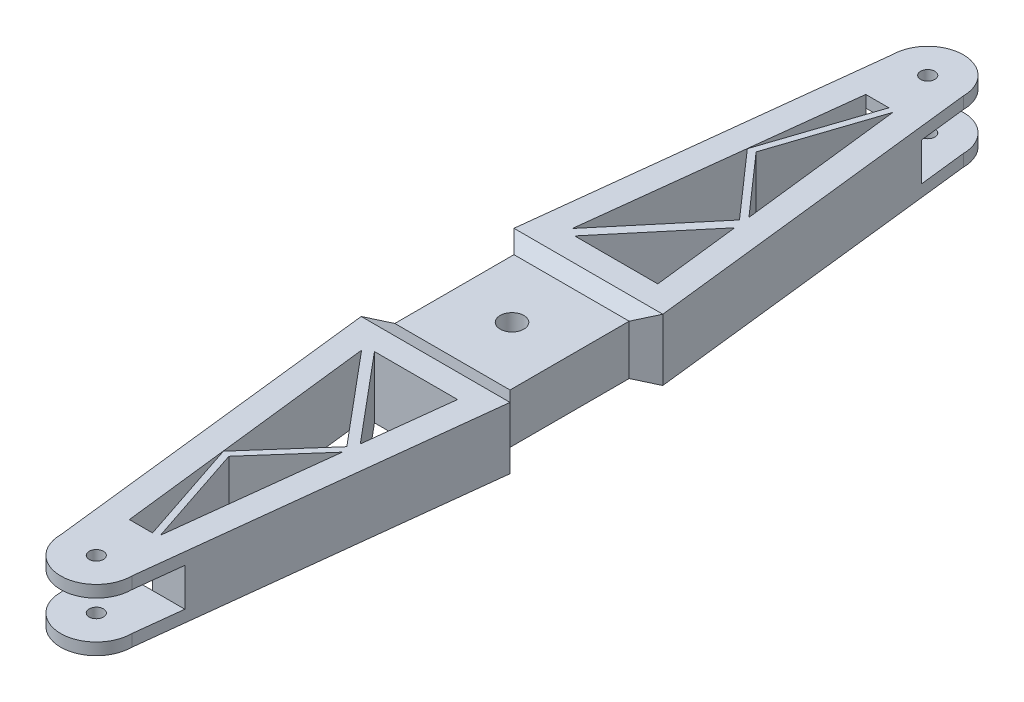
SolidWorks part; units mm, degrees
material "ABS"
ref_plane "Front Plane" through (0, 0, 0) normal (0, 0, 1) x (1, 0, 0)
ref_plane "Top Plane" through (0, 0, 0) normal (0, 1, 0) x (1, 0, 0)
ref_plane "Right Plane" through (0, 0, 0) normal (1, 0, 0) x (0, 0, -1)
sketch "Sketch2" plane through (0, 0, 0) normal (0, 1, 0) x (1, 0, 0)
  line L0 (0, 0) -> (0, 3) construction
  line L1 (0, 175) -> (168.3275, 175) construction
  line L2 (168.3275, 175) -> (-205.8504, 175) construction
  line L3 (-15, 350) -> (-35, 175)
  line L4 (-35, 175) -> (-15, 0)
  line L5 (15, 350) -> (35, 175)
  line L6 (35, 175) -> (15, 0)
  line L7 (0, 335) -> (0, 350) construction
  line L8 (31.3255, 207.1517) -> (24.2545, 200.0806)
  line L9 (24.2545, 200.0806) -> (24.2545, 149.9194)
  line L10 (31.3255, 142.8483) -> (24.2545, 149.9194)
  line L11 (-31.3255, 142.8483) -> (-24.2545, 149.9194)
  line L12 (-24.2545, 200.0806) -> (-24.2545, 149.9194)
  line L13 (-31.3255, 207.1517) -> (-24.2545, 200.0806)
  circle A0 centre (0, 350) radius 3
  circle A1 centre (0, 0) radius 3
  arc A2 (15, 350) -> (-15, 350) centre (0, 350) ccw
  arc A3 (-15, 0) -> (15, 0) centre (0, 0) ccw
  circle A4 centre (0, 175) radius 5
  point P21 (24.2545, 175)
  dimension "D2" = 6
  dimension "D3" = 6
  dimension "D4" = 30
  dimension "D5" = 30
  dimension "D7" = 10
  dimension "D1" = 350
  dimension "D6" = 35
  dimension "D8" = 32.1517
  dimension "D9" = 10
extrude "Boss-Extrude1" add sketch "Sketch2" along normal blind 26 contours L4 A3 L6 L10 L9 L8 L5 A2 L3 L13 L12 L11 A4 A0 A1 region at (0, 0, -361.1487)
sketch "Sketch3" plane through (0, 0, 0) normal (1, 0, 0) x (0, 0, -1)
  line L0 (-15, 13) -> (370.2756, 13) construction
  line L1 (-15, 26) -> (-15, 0) construction
  line L3 (177.6378, 13) -> (177.6378, -89.1144) construction
  line L5 (-50, 21) -> (20, 21)
  line L6 (-50, 21) -> (-50, 5)
  line L7 (-50, 5) -> (20, 5)
  line L8 (20, 21) -> (20, 5)
  line L9 (-50, 21) -> (20, 5) construction
  line L10 (-50, 5) -> (20, 21) construction
  dimension "D1" = 16
  dimension "D2" = 35
extrude "Cut-Extrude1" cut sketch "Sketch3" against normal mid plane 55
sketch "Sketch4" plane through (0, 26, 0) normal (0, 1, 0) x (1, 0, 0)
  circle A0 centre (0, 175) radius 5
sketch "Sketch5" plane through (24.2545, 0, 0) normal (1, 0, 0) x (0, 0, -1)
  line L0 (149.9194, 13) -> (220.8721, 13) construction
  line L1 (149.9194, 26) -> (149.9194, 0) construction
  line L2 (175, 0) -> (175, 36.8039) construction
  line L3 (200.0806, 0) -> (149.9194, 0) construction
  line L4 (142.8483, 26) -> (149.9194, 23.4568)
  line L5 (149.9194, 23.4568) -> (200.0806, 23.4568)
  line L6 (142.8483, 26) -> (207.1517, 26)
  line L7 (207.1517, 26) -> (200.0806, 23.4568)
  line L8 (207.1517, 0) -> (200.0806, 2.5432)
  line L9 (149.9194, 2.5432) -> (200.0806, 2.5432)
  line L10 (142.8483, 0) -> (149.9194, 2.5432)
  line L11 (142.8483, 0) -> (207.1517, 0)
  point P14 (175, 23.4568)
  point P15 (175, 26)
  point P19 (149.9194, 26)
  point P20 (142.8483, 26)
  point P22 (149.9194, 23.4568)
extrude "Cut-Extrude2" cut sketch "Sketch5" against normal mid plane 126
sketch "Sketch6" plane through (0, 26, 0) normal (0, 1, 0) x (1, 0, 0)
  line L0 (-53.994, 175) -> (45.9141, 175) construction
  line L1 (0, 0) -> (-15, 0)
  line L2 (-15, 0) -> (-30.9059, 139.177)
  line L3 (-31.3255, 142.8483) -> (-15, 0) construction
  line L4 (0, 0) -> (0, 374.1307) construction
  line L5 (-30.9059, 139.177) -> (0, 139.177)
  line L6 (0, 20) -> (-6.0778, 20)
  line L7 (-6.0778, 20) -> (-19.2259, 132.8483)
  line L8 (-19.2259, 132.8483) -> (0, 132.8483)
  line L9 (19.2259, 132.8483) -> (0, 132.8483)
  line L10 (0, 20) -> (6.0778, 20)
  line L11 (6.0778, 20) -> (19.2259, 132.8483)
  line L12 (-31.3255, 142.8483) -> (31.3255, 142.8483) construction
  point P16 (0, 135.8456)
  point P18 (0, 0)
  dimension "D1" = 20
  dimension "D2" = 10
extrude "Cut-Extrude3" cut sketch "Sketch6" against normal blind 61 contours L10 L11 L9 L8 L7 L6 region at (0, 26, -86.1971)
sketch "Sketch7" plane through (0, 26, 0) normal (0, 1, 0) x (1, 0, 0)
  line L5 (7.4654, 16.9423) -> (-8.2057, 64.0277)
  line L6 (-8.2057, 64.0277) -> (17.4723, 93.1846)
  line L7 (17.4723, 93.1846) -> (-17.4205, 134.8351)
  line L8 (3.6674, 20) -> (-11.2157, 64.7178)
  line L9 (-11.2157, 64.7178) -> (13.1145, 92.3443)
  line L10 (13.1145, 92.3443) -> (-20.3948, 132.3433)
  line L11 (3.6674, 20) -> (7.4654, 20)
  line L12 (-6.0778, 20) -> (6.0778, 20) construction
  line L13 (7.4654, 20) -> (7.4654, 16.9423)
  line L14 (-17.4205, 134.8351) -> (-20.3948, 134.8351)
  line L15 (-20.3948, 134.8351) -> (-20.3948, 132.3433)
  point P0 (3.7842, 9.649)
  line M2 (6.0778, 20) -> (-6.0778, 20)
  line M4 (-6.0778, 20) -> (-19.2259, 132.8483)
  line M6 (-19.2259, 132.8483) -> (19.2259, 132.8483)
  line M8 (19.2259, 132.8483) -> (6.0778, 20)
  dimension "D4" = 23.8601
  dimension "D5" = 27.6581
  dimension "D6" = 62.651
extrude "Boss-Extrude2" add sketch "Sketch7" against normal up to surface (26 mm away) contours L10 L9 L8 L5 L6 L7 M4 M2 M8 M6 region at (4.9545, 26, -20.5481) up to face at (0, 0, -76.4241)
ref_plane "Plane1" through (0, 0, -175) normal (0, 0, 1) x (1, 0, 0)
mirror "Mirror1" about plane through (0, 0, -175) normal (0, 0, 1) of "Boss-Extrude2", "Cut-Extrude3"
mirror "Mirror3" about plane through (0, 0, -175) normal (0, 0, 1) of "Cut-Extrude1"
